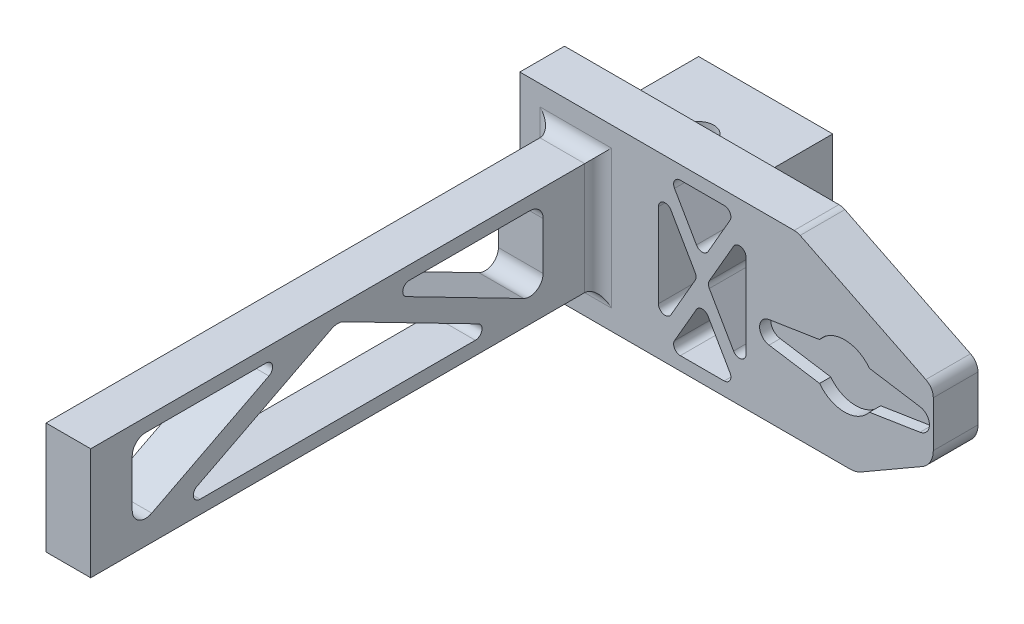
SolidWorks part; units mm, degrees
material "PLA"
ref_plane "Front Plane" through (0, 0, 0) normal (0, 0, 1) x (1, 0, 0)
ref_plane "Top Plane" through (0, 0, 0) normal (0, 1, 0) x (1, 0, 0)
ref_plane "Right Plane" through (0, 0, 0) normal (1, 0, 0) x (0, 0, -1)
sketch "Sketch3" plane through (0, 0, 0) normal (0, 0, 1) x (1, 0, 0)
  line L1 (-22.6388, -7.4411) -> (19.8612, -7.4411)
  line L2 (-22.6388, -7.4411) -> (-22.6388, 7.5589)
  line L3 (-22.6388, 7.5589) -> (19.8612, 7.5589)
  line L4 (19.8612, -7.4411) -> (19.8612, 7.5589)
  dimension "D1" = 15
  dimension "D2" = 42.5
extrude "Boss-Extrude1" add sketch "Sketch3" against normal blind 10
sketch "Sketch2" plane through (0, 0, 0) normal (0, 0, 1) x (1, 0, 0)
  line L0 (-16.8881, 2.4697) -> (-3.9686, 4.5)
  line L1 (-16.8881, -2.4697) -> (-3.9686, -4.5)
  line L2 (3.9686, 4.5) -> (16.8881, 2.4697)
  line L3 (16.8881, -2.4697) -> (3.9686, -4.5)
  line L4 (-16.9657, 2.9636) -> (-4.187, 4.9718)
  line L5 (4.187, 4.9718) -> (16.9657, 2.9636)
  line L6 (16.9657, -2.9636) -> (4.187, -4.9718)
  line L7 (-16.9657, -2.9636) -> (-4.187, -4.9718)
  arc A0 (-16.8881, 2.4697) -> (-16.8881, -2.4697) centre (-16.5, 0) ccw
  arc A1 (-3.9686, 4.5) -> (3.9686, 4.5) centre (0, 0) cw
  arc A2 (-3.9686, -4.5) -> (3.9686, -4.5) centre (0, 0) ccw
  arc A3 (16.8881, -2.4697) -> (16.8881, 2.4697) centre (16.5, 0) ccw
  arc A4 (-4.187, 4.9718) -> (4.187, 4.9718) centre (0, 0) cw
  arc A5 (16.9657, -2.9636) -> (16.9657, 2.9636) centre (16.5, 0) ccw
  arc A6 (-4.187, -4.9718) -> (4.187, -4.9718) centre (0, 0) ccw
  arc A7 (-16.9657, 2.9636) -> (-16.9657, -2.9636) centre (-16.5, 0) ccw
  circle A8 centre (0, 0) radius 7.0126
  dimension "D1" = 0.5
extrude "Cut-Extrude1" cut sketch "Sketch2" against normal blind 2.5 contours L3 A2 L1 A0 L0 A1 L2 A3 | A8
sketch "Sketch11" plane through (0, -7.4411, 0) normal (0, -1, 0) x (1, 0, 0)
  line L0 (8.25, 0) -> (-8.25, 0) construction
  line L1 (19.8612, -10) -> (-22.6388, -10)
  line L2 (19.8612, -10) -> (19.8612, 0)
  line L3 (19.8612, 0) -> (-22.6388, 0)
  line L4 (-22.6388, -10) -> (-22.6388, 0)
  line L5 (-22.6388, -10) -> (-22.6388, 0) construction
extrude "Boss-Extrude5" add sketch "Sketch11" along normal blind 10
sketch "Sketch14" plane through (0, 7.5589, 0) normal (0, 1, 0) x (1, 0, 0)
  line L0 (-8.25, 0) -> (8.25, 0) construction
  line L1 (19.8612, 10) -> (-22.6388, 10)
  line L2 (19.8612, 10) -> (19.8612, 0)
  line L3 (19.8612, 0) -> (-22.6388, 0)
  line L4 (-22.6388, 10) -> (-22.6388, 0)
  line L5 (-22.6388, 10) -> (-22.6388, 0) construction
extrude "Boss-Extrude7" add sketch "Sketch14" along normal blind 15
sketch "Sketch20" plane through (-22.6388, 0, 0) normal (-1, 0, 0) x (0, 0, 1)
  line L0 (0, -8.25) -> (0, 8.25) construction
  line L1 (-10, 22.5589) -> (0, 22.5589)
  line L2 (-10, 22.5589) -> (-10, -17.4411)
  line L3 (-10, -17.4411) -> (0, -17.4411)
  line L4 (0, 22.5589) -> (0, -17.4411)
  line L5 (0, -17.4411) -> (-10, -17.4411) construction
extrude "Boss-Extrude10" add sketch "Sketch20" along normal blind 50
sketch "Sketch21" plane through (0, 0, 0) normal (0, 0, 1) x (1, 0, 0)
  line L1 (-65.1388, 15.0589) -> (-55.1388, 15.0589)
  line L2 (-65.1388, 15.0589) -> (-65.1388, -9.9411)
  line L3 (-65.1388, -9.9411) -> (-55.1388, -9.9411)
  line L4 (-55.1388, 15.0589) -> (-55.1388, -9.9411)
  line L5 (-72.6388, 22.5589) -> (19.8612, 22.5589) construction
  line L6 (-72.6388, -17.4411) -> (-72.6388, 22.5589) construction
  dimension "D1" = 7.5
  dimension "D2" = 25
  dimension "D3" = 7.5
  dimension "D4" = 10
extrude "Boss-Extrude11" add sketch "Sketch21" along normal blind 113.5
sketch "Sketch22" plane through (0, 0, -10) normal (0, 0, -1) x (-1, 0, 0)
  line L0 (72.6388, 22.5589) -> (72.6388, -17.4411) construction
  line L1 (42.6388, 5.5589) -> (72.6388, 5.5589)
  line L2 (42.6388, 5.5589) -> (42.6388, -0.4411)
  line L3 (42.6388, -0.4411) -> (72.6388, -0.4411)
  line L4 (72.6388, 5.5589) -> (72.6388, -0.4411)
  line L5 (42.6388, 5.5589) -> (72.6388, -0.4411) construction
  line L6 (42.6388, -0.4411) -> (72.6388, 5.5589) construction
  line L7 (72.6388, -17.4411) -> (-19.8612, -17.4411) construction
  point P0 (57.6388, 2.5589)
  dimension "D1" = 20
  dimension "D2" = 30
  dimension "D3" = 6
extrude "Boss-Extrude12" add sketch "Sketch22" along normal blind 30
sketch "Sketch23" plane through (0, -0.4411, 0) normal (0, -1, 0) x (1, 0, 0)
  line L1 (-72.6388, -10) -> (-42.6388, -10)
  line L2 (-72.6388, -10) -> (-72.6388, -40)
  line L3 (-72.6388, -40) -> (-42.6388, -40)
  line L4 (-42.6388, -10) -> (-42.6388, -40)
extrude "Boss-Extrude13" add sketch "Sketch23" along normal blind 8.5
fillet "Fillet1" radius 3 4 edges at (-60.1388, 15.0589, 0) (-65.1388, 2.5589, 0) (-55.1388, 2.5589, 0) (-60.1388, -9.9411, 0)
chamfer "Chamfer1" distance 15 angle 63.75 1 edges at (19.8612, 22.5589, -5) first distance on face at (19.8612, 2.5589, -5)
fillet "Fillet2" radius 3 2 edges at (-10.5558, 22.5589, -5) (19.8612, 7.5589, -5)
chamfer "Chamfer2" distance 10 angle 60 1 edges at (19.8612, -17.4411, -5) first distance on face at (19.8612, -5.8739, -5)
fillet "Fillet3" radius 5 2 edges at (2.5406, -17.4411, -5) (19.8612, -7.4411, -5)
sketch "Sketch24" plane through (-65.1388, 0, 0) normal (-1, 0, 0) x (0, 0, 1)
  line L0 (58.25, 15.0589) -> (58.25, -9.9411) construction
  line L1 (113.5, 15.0589) -> (3, 15.0589) construction
  line L2 (113.5, -9.9411) -> (3, -9.9411) construction
  line L3 (58.25, -6.9411) -> (95.25, -6.9411)
  line L4 (58.25, -6.9411) -> (21.25, -6.9411)
  line L5 (21.25, -6.9411) -> (58.25, 12.0589)
  line L6 (58.25, 12.0589) -> (95.25, -6.9411)
  line L7 (48.399, 12.0589) -> (12.29, -6.4835)
  line L8 (48.399, 12.0589) -> (12.29, 12.0589)
  line L9 (12.29, 12.0589) -> (12.29, -6.4835)
  line L10 (68.101, 12.0589) -> (104.21, 12.0589)
  line L11 (68.101, 12.0589) -> (104.21, -6.4835)
  line L12 (104.21, 12.0589) -> (104.21, -6.4835)
  dimension "D1" = 37
  dimension "D2" = 37
  dimension "D3" = 3
  dimension "D4" = 3
  dimension "D5" = 3
  dimension "D6" = 4.5
  dimension "D7" = 18.5424
extrude "Cut-Extrude2" cut sketch "Sketch24" against normal through all
fillet "Fillet4" radius 3 5 edges at (-60.1388, -6.4835, 12.29) (-60.1388, 12.0589, 12.29) (-60.1388, -6.4835, 104.21) (-60.1388, 12.0589, 104.21) (-60.1388, 12.0589, 58.25)
fillet "Fillet5" radius 1.5 4 edges at (-60.1388, 12.0589, 68.101) (-60.1388, -6.9411, 95.25) (-60.1388, -6.9411, 21.25) (-60.1388, 12.0589, 48.399)
sketch "Sketch30" plane through (0, 5.5589, 0) normal (0, 1, 0) x (1, 0, 0)
  line L0 (-72.6388, 40) -> (-42.6388, 10) construction
  line L1 (-42.6388, 40) -> (-72.6388, 10) construction
  point P10 (-57.6388, 25)
hole_wizard "M8 Tapped Hole1" positions "Sketch30" profile "Sketch31" tap size "M8" standard "ISO"
sketch "Sketch31" plane through (-57.6388, 5.5589, -25) normal (1, 0, 0) x (0, 0, 1)
  line L0 (0, 0) -> (0, 24.2929)
  line L1 (0, 24.2929) -> (3.4, 22.25)
  line L2 (3.4, 22.25) -> (3.4, 0)
  line L5 (3.4, 0) -> (0, 0)
  line L10 (0, 24.2929) -> (-3.4, 22.25) construction
  line L11 (0, -6.35) -> (0, 107.95) construction
  dimension "Tap Drill Dia." = 6.8
  dimension "Tap Drill Depth" = 22.25
  dimension "Drill Angle" = 118
cosmetic thread "Hole Thread1" parameters "D1"=16, "D2"=8
ref_plane "Plane1" through (-42.6388, 5.5589, -10) normal (0, 0, 1) x (1, 0, 0)
sketch "Sketch32" plane through (-42.6388, 5.5589, -10) normal (0, 0, 1) x (1, 0, 0)
  line L0 (31.3835, 17) -> (-30, 17) construction
  line L1 (1, 14) -> (20.6191, 14) construction
  line L2 (1, 14) -> (1, -20) construction
  line L3 (1, -20) -> (20.6191, -20) construction
  line L4 (20.6191, 14) -> (20.6191, -20) construction
  line L5 (-30, -23) -> (43.8397, -23) construction
  line L6 (0, 0) -> (0, -14.5) construction
  line L7 (20.6191, 14) -> (1, -20) construction
  line L8 (20.6191, -20) -> (1, 14) construction
  line L9 (10.8096, 14) -> (3.3096, 14)
  line L10 (3.3096, 14) -> (10.8096, 1.0025)
  line L11 (10.8096, 1.0025) -> (18.3096, 14)
  line L12 (18.3096, 14) -> (10.8096, 14)
  line L13 (1, 12) -> (9.6555, -3)
  line L14 (9.6555, -3) -> (1, -18)
  line L15 (1, -18) -> (1, -3)
  line L16 (1, -3) -> (1, 12)
  line L17 (20.6191, -3) -> (1, -3) construction
  line L18 (10.8096, -20) -> (10.8096, 14) construction
  line L19 (10.8096, -7.0025) -> (18.3096, -20)
  line L20 (3.3096, -20) -> (10.8096, -7.0025)
  line L21 (10.8096, -20) -> (3.3096, -20)
  line L22 (18.3096, -20) -> (10.8096, -20)
  line L23 (20.6191, -18) -> (20.6191, -3)
  line L24 (11.9636, -3) -> (20.6191, -18)
  line L25 (20.6191, 12) -> (11.9636, -3)
  line L26 (20.6191, -3) -> (20.6191, 12)
  dimension "D1" = 3
  dimension "D2" = 3
  dimension "D3" = 1
  dimension "D4" = 7.5
  dimension "D5" = 7.5
  dimension "D6" = 3
  dimension "D7" = 15
  dimension "D8" = 15
extrude "Cut-Extrude3" cut sketch "Sketch32" along normal through all
fillet "Fillet6" radius 1.5 12 edges at (-41.6388, 17.5589, -5) (-31.8293, 6.5614, -5) (-39.3293, 19.5589, -5) (-24.3293, 19.5589, -5) (-22.0197, -12.4411, -5) (-22.0197, 17.5589, -5) (-30.6752, 2.5589, -5) (-39.3293, -14.4411, -5) (-24.3293, -14.4411, -5) (-31.8293, -1.4436, -5) (-41.6388, -12.4411, -5) (-32.9834, 2.5589, -5)
